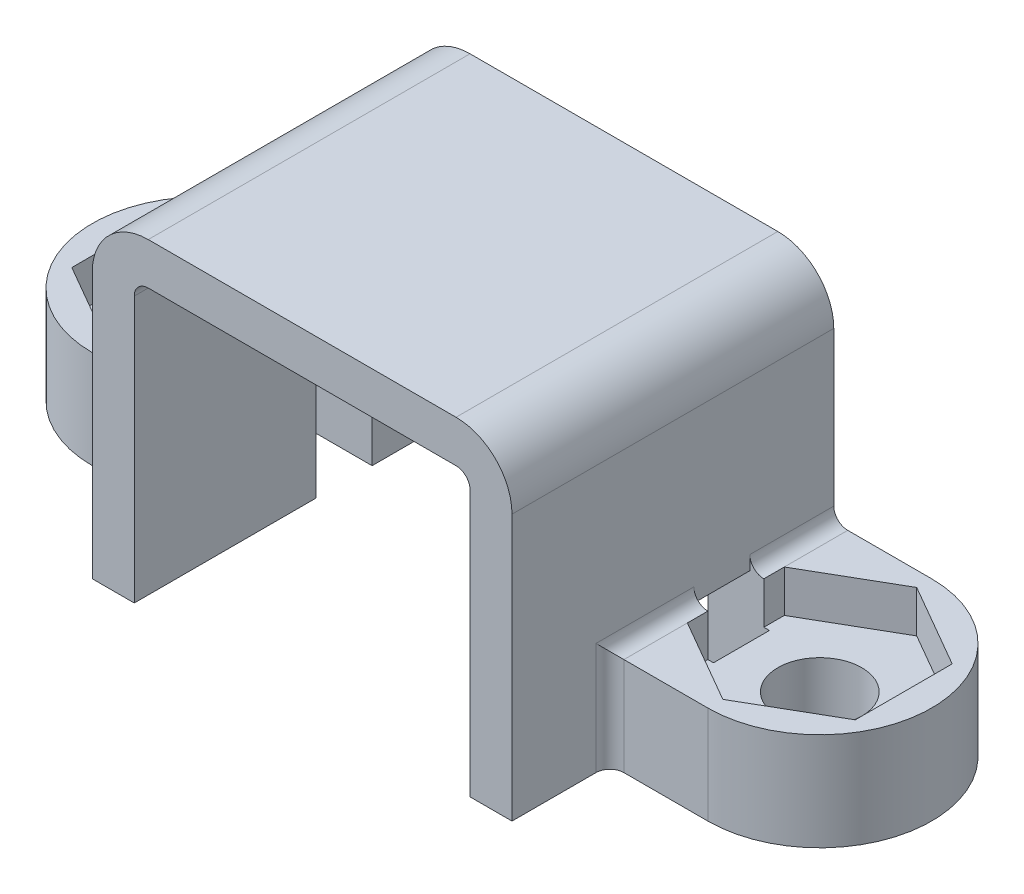
SolidWorks part; units mm, degrees
ref_plane "Front Plane" through (0, 0, 0) normal (0, 0, 1) x (1, 0, 0)
ref_plane "Top Plane" through (0, 0, 0) normal (0, 1, 0) x (1, 0, 0)
ref_plane "Right Plane" through (0, 0, 0) normal (1, 0, 0) x (0, 0, -1)
sketch "Sketch1" plane through (0, 0, 0) normal (0, 1, 0) x (1, 0, 0)
  line L1 (7.5, -5.75) -> (-7.5, -5.75)
  line L2 (7.5, -5.75) -> (7.5, 5.75)
  line L3 (7.5, 5.75) -> (-7.5, 5.75)
  line L4 (-7.5, -5.75) -> (-7.5, 5.75)
  line L5 (7.5, -5.75) -> (-7.5, 5.75) construction
  line L6 (7.5, 5.75) -> (-7.5, -5.75) construction
  point P0 (0, 0)
  dimension "D1" = 15
  dimension "D2" = 11.5
extrude "Boss-Extrude1" add sketch "Sketch1" along normal blind 1.5
sketch "Sketch4" plane through (0, 0, 0) normal (0, -1, 0) x (1, 0, 0)
  line L0 (-7.5, 5.75) -> (7.5, 5.75) construction
  line L1 (-7.5, -5.75) -> (-6, -5.75)
  line L2 (-7.5, -5.75) -> (-7.5, 5.75)
  line L3 (-7.5, 5.75) -> (-6, 5.75)
  line L4 (-6, -5.75) -> (-6, 5.75)
  line L6 (7.5, -5.75) -> (6, -5.75)
  line L7 (7.5, -5.75) -> (7.5, 5.75)
  line L8 (7.5, 5.75) -> (6, 5.75)
  line L9 (6, -5.75) -> (6, 5.75)
  dimension "D1" = 1.5
  dimension "D2" = 1.5
extrude "Boss-Extrude2" add sketch "Sketch4" along normal blind 10
ref_plane "Plane1" through (0, 0, 0) normal (1, 0, 0) x (0, 0, -1)
sketch "Sketch5" plane through (0, -10, 0) normal (0, -1, 0) x (1, 0, 0)
  line L0 (-6, -5.75) -> (-11, -5.75)
  line L1 (-6, 2.25) -> (-11, 2.25)
  line L2 (-6, -5.75) -> (-6, 5.75) construction
  line L3 (0, -5.5) -> (0, 5.5) construction
  line L4 (6, -5.75) -> (11, -5.75)
  line L5 (6, 2.25) -> (11, 2.25)
  line L6 (-6, 2.25) -> (-6, -5.75)
  line L7 (6, 2.25) -> (6, -5.75)
  arc A0 (-11, 2.25) -> (-11, -5.75) centre (-11, -1.75) ccw
  arc A1 (11, 2.25) -> (11, -5.75) centre (11, -1.75) cw
  dimension "D1" = 8
  dimension "D2" = 5
extrude "Boss-Extrude3" add sketch "Sketch5" against normal blind 3.5
sketch "Sketch11" plane through (-6, 0, 0) normal (1, 0, 0) x (0, 0, -1)
  line L0 (5.75, -10) -> (-5.75, -10) construction
  line L1 (2.75, -10) -> (0.75, -10)
  line L2 (2.75, -10) -> (2.75, -6.5)
  line L3 (2.75, -6.5) -> (0.75, -6.5)
  line L4 (0.75, -10) -> (0.75, -6.5)
  line L5 (5.75, -10) -> (5.75, 0) construction
  dimension "D1" = 3
  dimension "D2" = 2
  dimension "D3" = 3.5
extrude "Cut-Extrude2" cut sketch "Sketch11" against normal blind 2.2
sketch "Sketch10" plane through (0, -6.5, 0) normal (0, 1, 0) x (1, 0, 0)
  line L7 (-8, 3.4821) -> (-11, 5.2141)
  line L8 (-11, 5.2141) -> (-14, 3.4821)
  line L9 (-14, 3.4821) -> (-14, 0.0179)
  line L10 (-14, 0.0179) -> (-11, -1.7141)
  line L11 (-11, -1.7141) -> (-8, 0.0179)
  line L12 (-8, 0.0179) -> (-8, 3.4821)
  circle A0 centre (-11, 1.75) radius 3 construction
  arc A1 (-11, 5.75) -> (-11, -2.25) centre (-11, 1.75) ccw construction
  dimension "D1" = 6
extrude "Cut-Extrude1" cut sketch "Sketch10" against normal blind 1.5
sketch "Sketch12" plane through (0, -6.5, 0) normal (0, 1, 0) x (1, 0, 0)
  circle A0 centre (-11, 1.75) radius 1.5
  arc A1 (-11, 5.75) -> (-11, -2.25) centre (-11, 1.75) ccw construction
  dimension "D1" = 3
extrude "Cut-Extrude3" cut sketch "Sketch12" against normal through all
mirror "Mirror1" about plane through (0, 0, 0) normal (1, 0, 0) of "Cut-Extrude2", "Cut-Extrude1", "Cut-Extrude3"
fillet "Fillet1" radius 2 2 edges at (7.5, 1.5, 0) (-7.5, 1.5, 0)
fillet "Fillet2" radius 0.5 8 edges at (7.5, -6.5, -4.25) (7.5, -6.5, 0.75) (-7.5, -6.5, 0.75) (-7.5, -6.5, -4.25) (6, 0, 0) (-6, 0, 0) (7.5, -8.25, 2.25) (-7.5, -8.25, 2.25)
